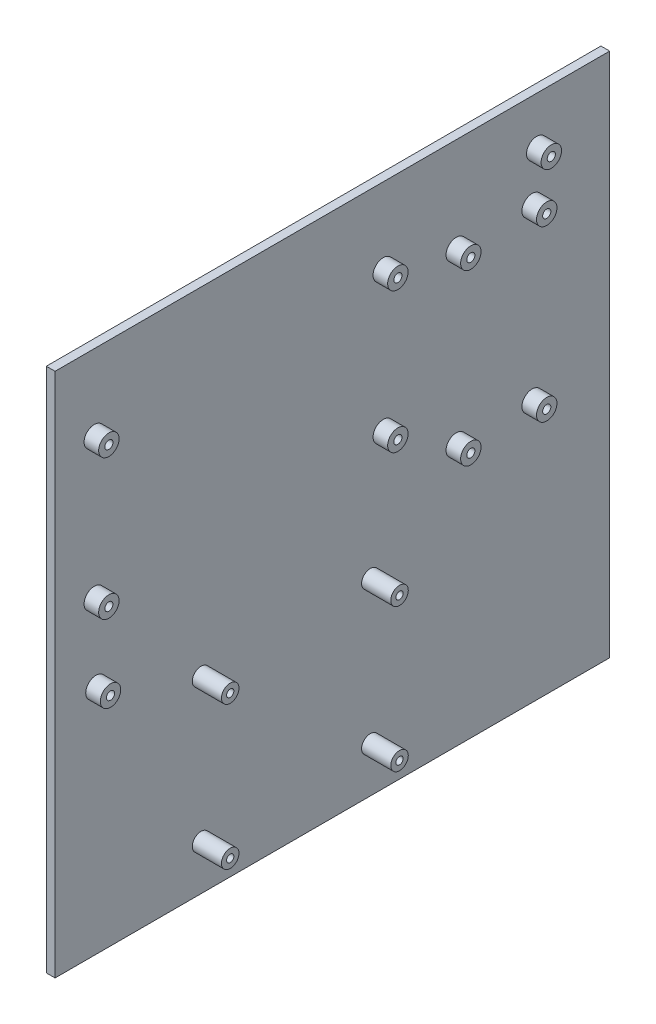
SolidWorks part; units mm, degrees
ref_plane "Front Plane" through (0, 0, 0) normal (0, 0, 1) x (1, 0, 0)
ref_plane "Top Plane" through (0, 0, 0) normal (0, 1, 0) x (1, 0, 0)
ref_plane "Right Plane" through (0, 0, 0) normal (1, 0, 0) x (0, 0, -1)
sketch "Sketch1" plane through (0, 0, 0) normal (1, 0, 0) x (0, 0, -1)
  line L1 (95, 90) -> (-95, 90)
  line L2 (95, 90) -> (95, -90)
  line L3 (95, -90) -> (-95, -90)
  line L4 (-95, 90) -> (-95, -90)
  line L5 (95, 90) -> (-95, -90) construction
  line L6 (95, -90) -> (-95, 90) construction
  point P0 (0, 0)
  point P7 (0, 0)
  dimension "D1" = 190
  dimension "D2" = 180
extrude "Boss-Extrude1" add sketch "Sketch1" along normal blind 3
sketch "Sketch2" plane through (3, 0, 0) normal (1, 0, 0) x (0, 0, -1)
  line L0 (95, 90) -> (-95, 90) construction
  line L1 (74, 80) -> (-85, 80) construction
  line L2 (74, 80) -> (74, -17) construction
  line L3 (74, -17) -> (-85, -17) construction
  line L4 (-85, 80) -> (-85, -17) construction
  line L5 (74, 80) -> (-85, -17) construction
  line L6 (74, -17) -> (-85, 80) construction
  line L7 (-95, 90) -> (-95, -90) construction
  line L9 (68.4363, 57.5311) -> (42.4363, 57.5311) construction
  line L10 (68.4363, 57.5311) -> (68.4363, -0.4689) construction
  line L11 (68.4363, -0.4689) -> (42.4363, -0.4689) construction
  line L12 (42.4363, 57.5311) -> (42.4363, -0.4689) construction
  line L13 (68.4363, 57.5311) -> (42.4363, -0.4689) construction
  line L14 (68.4363, -0.4689) -> (42.4363, 57.5311) construction
  line L15 (-81.5637, 64) -> (17.4363, 64) construction
  line L16 (-81.5637, 64) -> (-81.5637, 16) construction
  line L17 (-81.5637, 16) -> (17.4363, 16) construction
  line L18 (17.4363, 64) -> (17.4363, 16) construction
  line L19 (-81.5637, 64) -> (17.4363, 16) construction
  line L20 (-81.5637, 16) -> (17.4363, 64) construction
  circle A0 centre (-81, -10.7) radius 1.4
  circle A1 centre (-81, -10.7) radius 3.5
  circle A2 centre (70, 73.7) radius 1.4
  circle A3 centre (70, 73.7) radius 3.5
  circle A4 centre (-81.5637, 64) radius 1.4
  circle A5 centre (17.4363, 64) radius 1.4
  circle A6 centre (17.4363, 16) radius 1.4
  circle A7 centre (-81.5637, 16) radius 1.4
  circle A8 centre (68.4363, -0.4689) radius 1.4
  circle A9 centre (42.4363, -0.4689) radius 1.4
  circle A10 centre (42.4363, 57.5311) radius 1.4
  circle A11 centre (68.4363, 57.5311) radius 1.4
  circle A12 centre (-81.5637, 64) radius 3.5
  circle A13 centre (17.4363, 64) radius 3.5
  circle A14 centre (42.4363, 57.5311) radius 3.5
  circle A15 centre (68.4363, 57.5311) radius 3.5
  circle A16 centre (42.4363, -0.4689) radius 3.5
  circle A17 centre (68.4363, -0.4689) radius 3.5
  circle A18 centre (17.4363, 16) radius 3.5
  circle A19 centre (-81.5637, 16) radius 3.5
  point P0 (-5.5, 31.5)
  point P15 (-32.0637, 40)
  point P19 (55.4363, 28.5311)
  point P41 (53.4846, 27)
  point P42 (-29.0741, 27)
  point P43 (58.7739, 28.5311)
  point P44 (-32.0637, 40)
  point P45 (0, 0)
  dimension "D5" = 2.8
  dimension "D6" = 7
  dimension "D1" = 159
  dimension "D2" = 97
  dimension "D3" = 10
  dimension "D4" = 10
  dimension "D7" = 6.3
  dimension "D8" = 6.3
  dimension "D9" = 4
  dimension "D10" = 4
  dimension "D11" = 26
  dimension "D12" = 58
  dimension "D13" = 99
  dimension "D14" = 48
  dimension "D15" = 50
  dimension "D16" = 25
extrude "Boss-Extrude2" add sketch "Sketch2" along normal blind 5
sketch "Sketch3" plane through (3, 0, 0) normal (1, 0, 0) x (0, 0, -1)
  line L1 (13, -25.5) -> (-45, -25.5) construction
  line L2 (13, -25.5) -> (13, -74.5) construction
  line L3 (13, -74.5) -> (-45, -74.5) construction
  line L4 (-45, -25.5) -> (-45, -74.5) construction
  line L5 (13, -25.5) -> (-45, -74.5) construction
  line L6 (13, -74.5) -> (-45, -25.5) construction
  line L7 (-95, -90) -> (95, -90) construction
  line L8 (95, -90) -> (95, 90) construction
  circle A0 centre (-45, -25.5) radius 1.25
  circle A1 centre (-45, -74.5) radius 1.25
  circle A2 centre (13, -25.5) radius 1.25
  circle A3 centre (13, -74.5) radius 1.25
  circle A4 centre (-45, -25.5) radius 3
  circle A5 centre (13, -25.5) radius 3
  circle A6 centre (-45, -74.5) radius 3
  circle A7 centre (13, -74.5) radius 3
  point P0 (-16, -50)
  dimension "D3" = 2.5
  dimension "D4" = 6
  dimension "D1" = 58
  dimension "D2" = 49
  dimension "D5" = 140
  dimension "D6" = 40
extrude "Boss-Extrude3" add sketch "Sketch3" along normal blind 10
